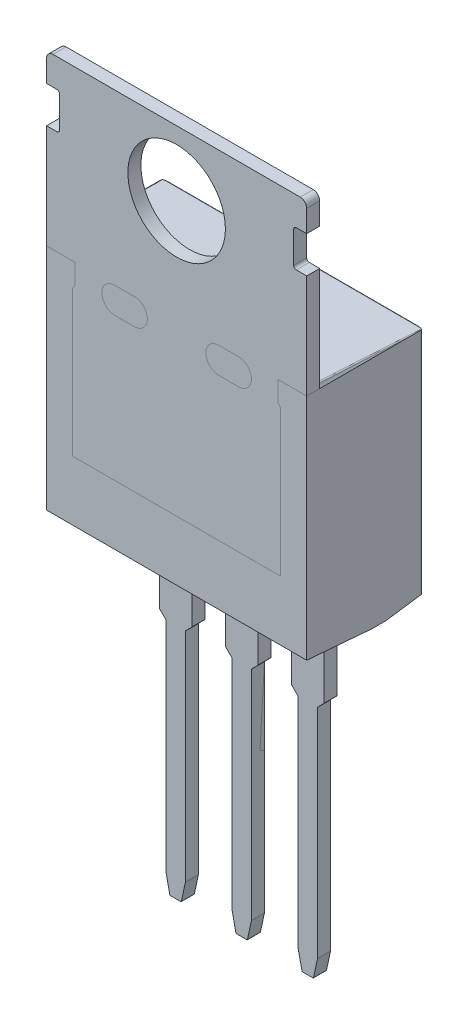
SolidWorks part; units mm, degrees
ref_plane "前视基准面" through (0, 0, 0) normal (0, 0, 1) x (1, 0, 0)
ref_plane "上视基准面" through (0, 0, 0) normal (0, 1, 0) x (1, 0, 0)
ref_plane "右视基准面" through (0, 0, 0) normal (1, 0, 0) x (0, 0, -1)
sketch "Sketch1" plane through (0, 0, 0) normal (1, 0, 0) x (0, 0, -1)
  line L1 (-2.25, -4.5) -> (2.25, -4.5)
  line L2 (-2.25, -4.5) -> (-2.25, 4.5)
  line L3 (-2.25, 4.5) -> (2.25, 4.5)
  line L4 (2.25, -4.5) -> (2.25, 4.5)
  line L5 (-2.25, -4.5) -> (2.25, 4.5) construction
  line L6 (-2.25, 4.5) -> (2.25, -4.5) construction
  point P0 (0, 0)
extrude "Boss-Extrude1" add sketch "Sketch1" along normal mid plane 10
sketch "Sketch2" plane through (0, 0, 2.25) normal (0, 0, 1) x (1, 0, 0)
  line L0 (0, 0) -> (0, 6.4228) construction
  line L1 (-4, -2) -> (4, -2)
  line L2 (4, -2) -> (4, 3.5893)
  line L3 (4, 3.5893) -> (3.9, 3.7386)
  line L4 (3.9, 3.7386) -> (3.9, 4.5)
  line L5 (5, 4.5) -> (-5, 4.5) construction
  line L6 (-3.9, 4.5) -> (-3.9, 5.5865)
  line L7 (-3.9, 3.7386) -> (-3.9, 4.5)
  line L8 (-4, 3.5893) -> (-3.9, 3.7386)
  line L9 (-4, -2) -> (-4, 3.5893)
  line L10 (-3.1117, -2) -> (-3.1117, -4.5) construction
  line L11 (5, -4.5) -> (-5, -4.5) construction
  line L12 (-3.9, 5.5865) -> (3.9, 5.5865)
  line L13 (3.9, 5.5865) -> (3.9, 4.5)
  line L14 (-2.375, 4) -> (-1.625, 4) construction
  line L15 (-2.375, 4.5) -> (-1.625, 4.5)
  line L16 (-2.375, 3.5) -> (-1.625, 3.5)
  line L17 (2.375, 4) -> (1.625, 4) construction
  line L18 (2.375, 4.5) -> (1.625, 4.5)
  line L19 (2.375, 3.5) -> (1.625, 3.5)
  line L20 (-1.125, 4) -> (1.125, 4) construction
  line L21 (1.125, 4) -> (1.125, 4.5) construction
  arc A0 (-2.375, 4.5) -> (-2.375, 3.5) centre (-2.375, 4) ccw
  arc A1 (-1.625, 3.5) -> (-1.625, 4.5) centre (-1.625, 4) ccw
  arc A2 (2.375, 4.5) -> (2.375, 3.5) centre (2.375, 4) cw
  arc A3 (1.625, 3.5) -> (1.625, 4.5) centre (1.625, 4) cw
  point P12 (0, 4.5)
  point P15 (0, -2)
  point P23 (-2, 4)
  point P31 (2, 4)
extrude "Cut-Extrude1" cut sketch "Sketch2" against normal blind 0.5
ref_plane "Plane1" through (0, 0, -0.25) normal (0, 0, -1) x (-1, 0, 0)
sketch "Sketch6" plane through (0, 0, 0) normal (1, 0, 0) x (0, 0, -1)
  line L0 (2.25, 4.5) -> (-1.75, 4.6524)
  line L1 (-1.75, 4.6524) -> (-1.75, 4.5)
  line L2 (-1.75, 4.5) -> (2.25, 4.5)
extrude "Boss-Extrude5" add sketch "Sketch6" along normal mid plane 9.8
fillet "Fillet5" radius 0.5 2 edges at (-4.9, 4.5, -0.25) (4.9, 4.5, -0.25)
fillet "Fillet6" radius 0.05 2 edges at (4.9546, 4.5728, -0.3379) (-4.9546, 4.5728, -0.3379)
sketch "Sketch7" plane through (5, 0, 0) normal (1, 0, 0) x (0, 0, -1)
  line L0 (0.25, -4.5) -> (-2.25, -4.5)
  line L1 (-2.25, -4.5) -> (2.25, -4.5) construction
  line L2 (-2.25, -4.5) -> (-2.25, -4.2954)
  line L3 (-2.25, 4.5) -> (-2.25, -4.5) construction
  line L4 (-2.25, -4.2954) -> (0.25, -4.5)
  line L5 (2.25, -4.5) -> (0.8, -4.5)
  line L6 (0.8, -4.5) -> (2.25, -4.2954)
  line L7 (2.25, -4.5) -> (2.25, 4.4937) construction
  line L8 (2.25, -4.2954) -> (2.25, -4.5)
  line L9 (0.8, -4.5) -> (0.25, -4.5) construction
extrude "Cut-Extrude2" cut sketch "Sketch7" against normal through all both and the other way through all
sketch "Sketch4" plane through (0, 0, -0.25) normal (0, 0, -1) x (-1, 0, 0)
  line L0 (0, -4.5) -> (0, -17.25) construction
  line L1 (-5, -4.5) -> (5, -4.5) construction
  line L2 (-0.6682, -4.5) -> (0.6682, -4.5)
  line L3 (0.6682, -4.5) -> (0.6682, -5.5)
  line L4 (0.625, -5.5) -> (0.6682, -5.5)
  line L5 (0.625, -5.5) -> (0.625, -7.9)
  line L6 (0.625, -7.9) -> (0.375, -8.15)
  line L7 (0.375, -8.15) -> (0.375, -16.5187)
  line L8 (0.375, -16.5187) -> (0.2184, -17.25)
  line L9 (0.2184, -17.25) -> (-0.2184, -17.25)
  line L10 (-0.375, -16.5187) -> (-0.2184, -17.25)
  line L11 (-0.375, -8.15) -> (-0.375, -16.5187)
  line L12 (-0.625, -7.9) -> (-0.375, -8.15)
  line L13 (-0.625, -5.5) -> (-0.625, -7.9)
  line L14 (-0.625, -5.5) -> (-0.6682, -5.5)
  line L15 (-0.6682, -4.5) -> (-0.6682, -5.5)
  line L16 (-0.375, -14.952) -> (0.375, -14.952) construction
  line L17 (-0.625, -7.9) -> (0.625, -7.9) construction
extrude "Boss-Extrude3" add sketch "Sketch4" along normal blind 0.5 separate body
fillet "Fillet2" radius 0.02 12 edges at (-0.625, -5.5, -0.5) (-0.6682, -5.5, -0.5) (-0.625, -7.9, -0.5) (-0.375, -8.15, -0.5) (-0.375, -16.5187, -0.5) (-0.2184, -17.25, -0.5) (0.2184, -17.25, -0.5) (0.375, -16.5187, -0.5) (0.375, -8.15, -0.5) (0.625, -7.9, -0.5) (0.625, -5.5, -0.5) (0.6682, -5.5, -0.5)
sketch "Sketch3" plane through (0, 0, 1.75) normal (0, 0, 1) x (1, 0, 0)
  line L1 (-5, 4.5) -> (-5, 11)
  line L2 (-5, 11) -> (5, 11)
  line L3 (0, 11) -> (0, 0) construction
  line L4 (3.9, 4.5) -> (5, 4.5)
  line L5 (5, 4.5) -> (5, 11)
  line L6 (1.875, 8.5) -> (1.875, 11) construction
  line L8 (2.375, 4.5) -> (1.625, 4.5)
  line L9 (-2.375, 3.5) -> (-1.625, 3.5)
  line L10 (-1.625, 4.5) -> (-2.375, 4.5)
  line L11 (-2.375, 3.5) -> (-1.625, 3.5)
  line L12 (-3.9, 4.5) -> (-3.9, 3.7386)
  line L13 (-3.9, 3.7386) -> (-4, 3.5893)
  line L14 (-4, 3.5893) -> (-4, -2)
  line L15 (-4, -2) -> (4, -2)
  line L16 (4, -2) -> (4, 3.5893)
  line L17 (4, 3.5893) -> (3.9, 3.7386)
  line L18 (3.9, 3.7386) -> (3.9, 4.5)
  line L19 (3.9, 4.5) -> (5, 4.5)
  line L20 (4.8867, 4.6524) -> (-4.8867, 4.6524)
  line L22 (-5, 4.5) -> (-3.9, 4.5)
  line L23 (-5, 4.5) -> (-3.9, 4.5)
  line L24 (-3.9, 4.5) -> (-3.9, 3.7386)
  line L25 (-3.9, 3.7386) -> (-4, 3.5893)
  line L26 (-4, 3.5893) -> (-4, -2)
  line L27 (-4, -2) -> (4, -2)
  line L28 (4, -2) -> (4, 3.5893)
  line L29 (4, 3.5893) -> (3.9, 3.7386)
  line L30 (3.9, 3.7386) -> (3.9, 4.5)
  line L31 (-1.625, 4.5) -> (-2.375, 4.5)
  line L32 (2.375, 4.5) -> (1.625, 4.5)
  line L33 (1.625, 3.5) -> (2.375, 3.5)
  line L35 (1.625, 3.5) -> (2.375, 3.5)
  circle A0 centre (0, 8.5) radius 1.875
  arc A3 (-2.375, 4.5) -> (-2.375, 3.5) centre (-2.375, 4) ccw
  arc A4 (4.9334, 4.6203) -> (5, 4.5) centre (5.4, 4.8) ccw
  arc A6 (4.9334, 4.6203) -> (4.8867, 4.6524) centre (4.8867, 4.6023) ccw
  arc A8 (-1.625, 3.5) -> (-1.625, 4.5) centre (-1.625, 4) ccw
  arc A9 (-2.375, 4.5) -> (-2.375, 3.5) centre (-2.375, 4) ccw
  arc A10 (-1.625, 3.5) -> (-1.625, 4.5) centre (-1.625, 4) ccw
  arc A11 (2.375, 3.5) -> (2.375, 4.5) centre (2.375, 4) ccw
  arc A12 (1.625, 4.5) -> (1.625, 3.5) centre (1.625, 4) ccw
  arc A13 (2.375, 3.5) -> (2.375, 4.5) centre (2.375, 4) ccw
  arc A14 (1.625, 4.5) -> (1.625, 3.5) centre (1.625, 4) ccw
  arc A17 (-4.8867, 4.6524) -> (-4.9334, 4.6203) centre (-4.8867, 4.6023) ccw
  arc A19 (-5, 4.5) -> (-4.9334, 4.6203) centre (-5.4, 4.8) ccw
  dimension "D2" = 0
  dimension "D1" = 0
  dimension "D3" = 0
extrude "Boss-Extrude2" add sketch "Sketch3" along normal blind 0.5 separate body
fillet "Fillet1" radius 0.25 2 edges at (-5, 11, 2) (5, 11, 2)
pattern_linear "LPattern1" count 2 spacing 2.54 along (-1, 0, 0) count 2 spacing 2.54 along (1, 0, 0) of "Boss-Extrude3", "Fillet2"
fillet "Fillet7" radius 0.5 2 edges at (-5, 0.0992, -2.25) (5, 0.0992, -2.25) second distance 0.1 first distance on face at (-0.0028, 1.5664, -2.25)
fillet "Fillet9" radius 0.05 1 edges tangent propagation no
sketch "Sketch11" plane through (0, 0, -2.25) normal (0, 0, -1) x (-1, 0, 0)
  text T0 "LM317" font "方正姚体" height in points 6
extrude "Boss-Extrude9" add sketch "Sketch11" along normal blind 0.0005 separate body
sketch "Sketch12" plane through (0, 0, 1.75) normal (0, 0, -1) x (-1, 0, 0)
  line L0 (5, 9.9062) -> (4.5, 9.9062)
  line L1 (5, 10.75) -> (5, 4.5) construction
  line L2 (-5, 9.9062) -> (-4.5, 9.9062)
  line L3 (-5, 4.5) -> (-5, 10.75) construction
  line L4 (-5, 9.9062) -> (-5, 8.5)
  line L5 (-5, 8.5) -> (-4.5, 8.5)
  line L6 (-4.5, 8.5) -> (-4.5, 9.9062)
  line L7 (4.5, 9.9062) -> (4.5, 8.5)
  line L8 (4.5, 8.5) -> (5, 8.5)
  line L9 (5, 8.5) -> (5, 9.9062)
extrude "Cut-Extrude3" cut sketch "Sketch12" against normal through all
fillet "Fillet10" radius 0.1 4 edges at (4.5, 9.9062, 2) (4.5, 8.5, 2) (-4.5, 9.9062, 2) (-4.5, 8.5, 2)
